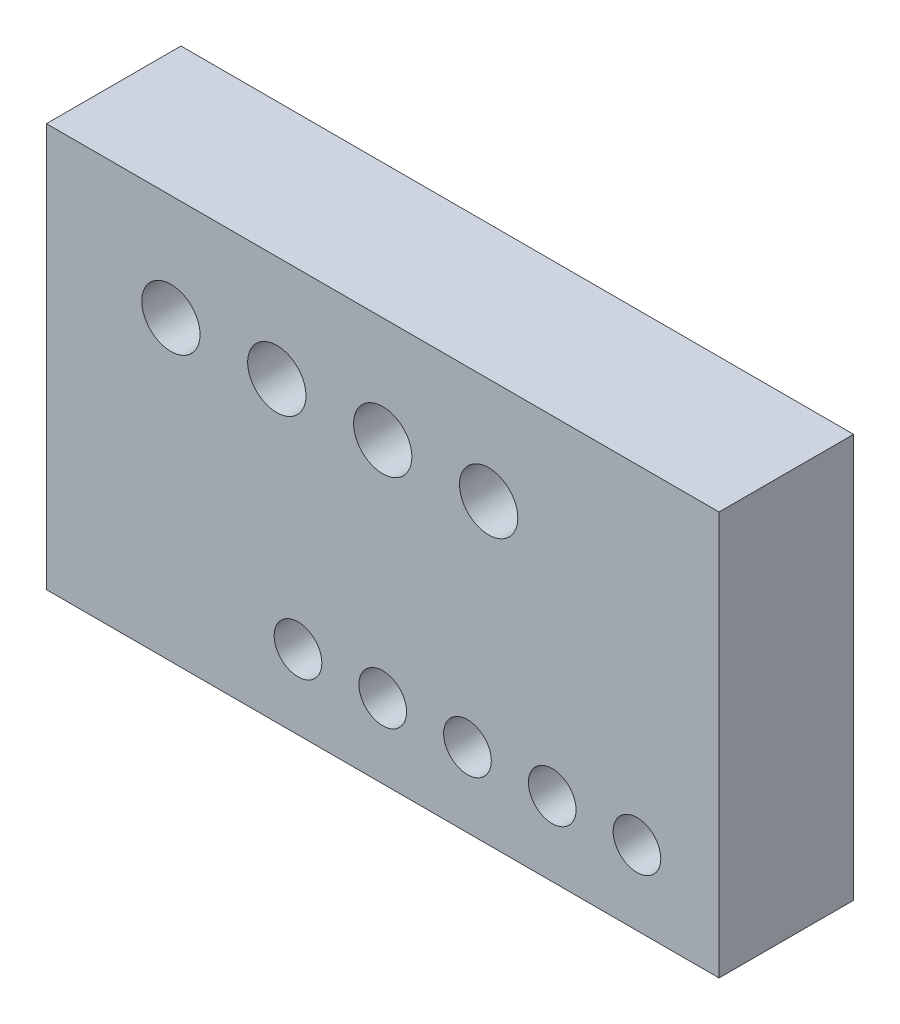
SolidWorks part; units mm, degrees
material "6061 Alloy"
ref_plane "Front Plane" through (0, 0, 0) normal (0, 0, 1) x (1, 0, 0)
ref_plane "Top Plane" through (0, 0, 0) normal (0, 1, 0) x (1, 0, 0)
ref_plane "Right Plane" through (0, 0, 0) normal (1, 0, 0) x (0, 0, -1)
sketch "Sketch1" plane through (0, 0, 0) normal (0, 0, 1) x (1, 0, 0)
  line L1 (31.75, -19.05) -> (-31.75, -19.05)
  line L2 (31.75, -19.05) -> (31.75, 19.05)
  line L3 (31.75, 19.05) -> (-31.75, 19.05)
  line L4 (-31.75, -19.05) -> (-31.75, 19.05)
  line L5 (31.75, -19.05) -> (-31.75, 19.05) construction
  line L6 (31.75, 19.05) -> (-31.75, -19.05) construction
  point P0 (0, 0)
  point P6 (0, -12.05)
  point P7 (-8, -12.05)
  point P8 (8, -12.05)
  point P9 (16, -12.05)
  point P10 (24, -12.05)
  point P11 (-10, 9.05)
  point P12 (0, 9.05)
  point P13 (10, 9.05)
  point P14 (-20, 9.05)
  dimension "D1" = 38.1
  dimension "D2" = 63.5
  dimension "D3" = 8
  dimension "D4" = 8
  dimension "D5" = 8
  dimension "D6" = 8
  dimension "D7" = 7
  dimension "D8" = 10
  dimension "D9" = 10
  dimension "D10" = 10
  dimension "D11" = 10
extrude "Boss-Extrude1" add sketch "Sketch1" along normal blind 12.7
hole_wizard "M4 Clearance Hole1" positions "Sketch2" profile "Sketch3" hole size "M4" standard "ANSI Metric" end condition through all
sketch "Sketch2" plane through (0, 0, 12.7) normal (0, 0, 1) x (1, 0, 0)
  point P0 (-8, -12.05)
  point P3 (0, -12.05)
  point P6 (8, -12.05)
  point P9 (16, -12.05)
  point P12 (24, -12.05)
sketch "Sketch3" plane through (-8, -12.05, 12.7) normal (1, 0, 0) x (0, -1, 0)
  line L0 (0, 0) -> (0, 12.7)
  line L1 (0, 12.7) -> (2.25, 12.7)
  line L2 (2.25, 12.7) -> (2.25, 0)
  line L5 (2.25, 0) -> (0, 0)
  line L11 (0, -6.35) -> (0, 107.95) construction
  dimension "Thru Hole Dia." = 4.5
  dimension "Thru Hole Depth" = 12.7
hole_wizard "M5 Clearance Hole1" positions "Sketch4" profile "Sketch5" hole size "M5" standard "ANSI Metric" end condition through all
sketch "Sketch4" plane through (0, 0, 12.7) normal (0, 0, 1) x (1, 0, 0)
  point P0 (-20, 9.05)
  point P3 (-10, 9.05)
  point P6 (0, 9.05)
  point P9 (10, 9.05)
sketch "Sketch5" plane through (-20, 9.05, 12.7) normal (1, 0, 0) x (0, -1, 0)
  line L0 (0, 0) -> (0, 12.7)
  line L1 (0, 12.7) -> (2.75, 12.7)
  line L2 (2.75, 12.7) -> (2.75, 0)
  line L5 (2.75, 0) -> (0, 0)
  line L11 (0, -6.35) -> (0, 107.95) construction
  dimension "Thru Hole Dia." = 5.5
  dimension "Thru Hole Depth" = 12.7
